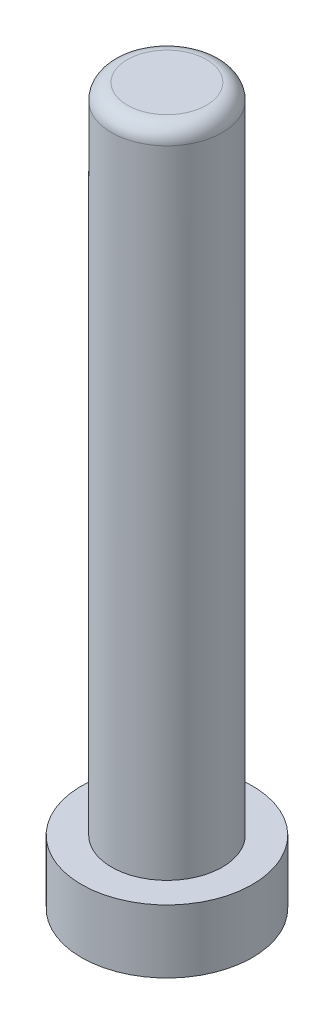
SolidWorks part; units mm, degrees
ref_plane "Front Plane" through (0, 0, 0) normal (0, 0, 1) x (1, 0, 0)
ref_plane "Top Plane" through (0, 0, 0) normal (0, 1, 0) x (1, 0, 0)
ref_plane "Right Plane" through (0, 0, 0) normal (1, 0, 0) x (0, 0, -1)
sketch "Sketch1" plane through (0, 0, 0) normal (0, 1, 0) x (1, 0, 0)
  line L1 (-2.8, -2.7) -> (2.8, -2.7) construction
  line L2 (-2.8, -2.7) -> (-2.8, 2.7) construction
  line L3 (-2.8, 2.7) -> (2.8, 2.7) construction
  line L4 (2.8, -2.7) -> (2.8, 2.7) construction
  line L5 (-2.8, -2.7) -> (2.8, 2.7) construction
  line L6 (-2.8, 2.7) -> (2.8, -2.7) construction
  circle A0 centre (0, 0) radius 2.7
  point P0 (0, 0)
  dimension "D1" = 5.6
  dimension "D2" = 5.4
extrude "Boss-Extrude1" add sketch "Sketch1" along normal blind 2
sketch "Sketch2" plane through (0, 2, 0) normal (0, 1, 0) x (1, 0, 0)
  circle A0 centre (0, 0) radius 1.75
  dimension "D1" = 3.5
sketch "Sketch3" plane through (0, 0, 0) normal (0, -1, 0) x (1, 0, 0)
  circle A0 centre (0, 0) radius 1.2
  circle A1 centre (0, 0) radius 0.95
  point P0 (0, 0)
  dimension "D1" = 2.4
  dimension "D2" = 1.9
extrude "Cut-Extrude2" cut sketch "Sketch3" against normal blind 9.5 contours A1
extrude "Boss-Extrude2" add sketch "Sketch2" along normal blind 20.6
sketch "Sketch7" plane through (0, 0, 0) normal (0, -1, 0) x (1, 0, 0)
  circle A0 centre (0, 0) radius 1.2
  dimension "D1" = 2.4
extrude "Cut-Extrude4" cut sketch "Sketch7" against normal blind 2.8
fillet "Fillet2" radius 0.5 1 edges at (0, 22.6, 1.75)
sketch "Sketch8" plane through (0, 0, 0) normal (0, -1, 0) x (1, 0, 0)
  circle A0 centre (0, 0) radius 0.95
  dimension "D1" = 1.9
extrude "Cut-Extrude5" cut sketch "Sketch8" against normal blind 9.5
